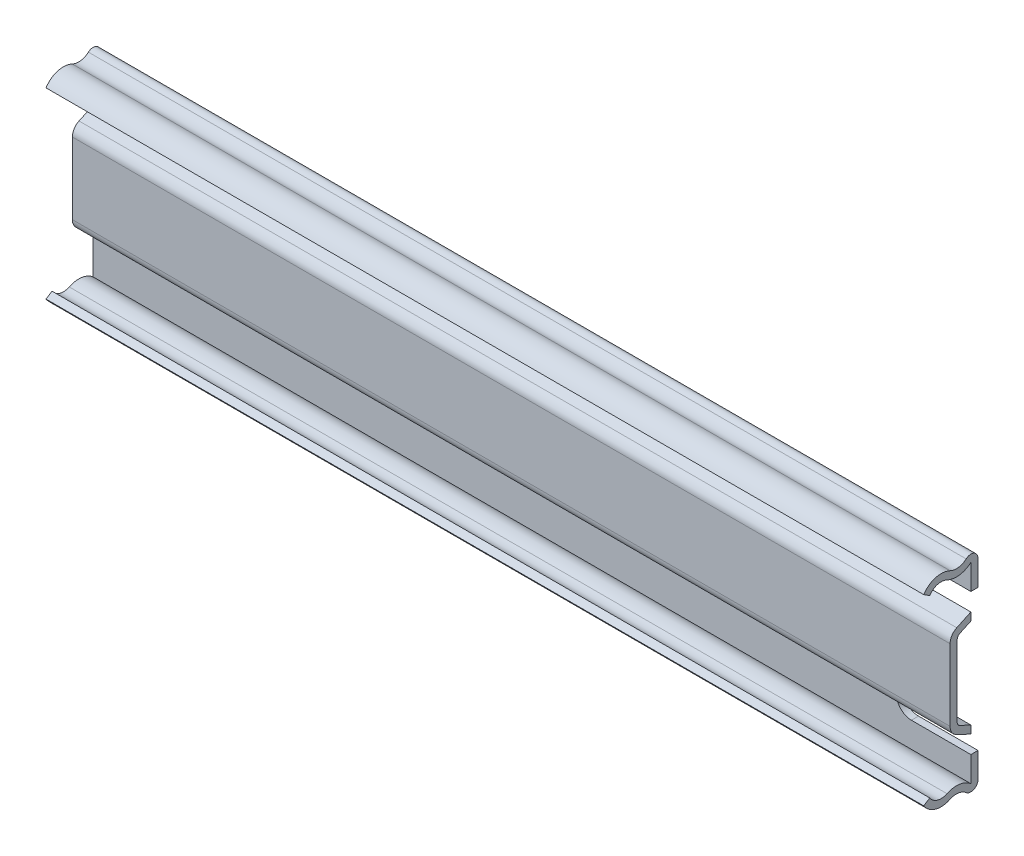
SolidWorks part; units mm, degrees
material "AISI 316 Annealed Stainless Steel Bar (SS)"
ref_plane "Front Plane" through (0, 0, 0) normal (0, 0, 1) x (1, 0, 0)
ref_plane "Top Plane" through (0, 0, 0) normal (0, 1, 0) x (1, 0, 0)
ref_plane "Right Plane" through (0, 0, 0) normal (1, 0, 0) x (0, 0, -1)
ref_plane "Plane1" through (-3.937, 0, 0) normal (1, 0, 0) x (0, 0, -1)
sketch "Sketch1" plane through (-3.937, 0, 0) normal (1, 0, 0) x (0, 0, -1)
  line L0 (2.3114, 16.3766) -> (2.3114, -16.3766)
  line L1 (-4.7105, -14.9753) -> (-5.7404, -15.6277)
  line L2 (3.5306, -16.3766) -> (3.5306, 16.3766)
  line L3 (-5.7404, 15.6277) -> (-4.7105, 14.9753)
  arc A0 (2.3114, -16.3766) -> (-1.7707, -15.816) centre (-0.1524, -19.1744) ccw
  arc A1 (-1.7707, -15.816) -> (-4.7105, -14.9753) centre (-2.7686, -13.7451) cw
  arc A2 (-5.7404, -15.6277) -> (-1.2415, -16.9143) centre (-2.7686, -13.7451) ccw
  arc A3 (-1.2415, -16.9143) -> (1.5056, -17.2916) centre (-0.1524, -19.1744) cw
  arc A4 (1.5056, -17.2916) -> (3.5306, -16.3766) centre (2.3114, -16.3766) ccw
  arc A5 (3.5306, 16.3766) -> (1.5056, 17.2916) centre (2.3114, 16.3766) ccw
  arc A6 (1.5056, 17.2916) -> (-1.2415, 16.9143) centre (-0.1524, 19.1744) cw
  arc A7 (-1.2415, 16.9143) -> (-5.7404, 15.6277) centre (-2.7686, 13.7451) ccw
  arc A8 (-4.7105, 14.9753) -> (-1.7707, 15.816) centre (-2.7686, 13.7451) cw
  arc A9 (-1.7707, 15.816) -> (2.3114, 16.3766) centre (-0.1524, 19.1744) ccw
  dimension "D1" = 3.728
  dimension "D2" = 2.2987
  dimension "D3" = 3.5179
  dimension "D4" = 1.2192
  dimension "D5" = 2.025
  dimension "D6" = 4.7721
  dimension "D7" = 8.2411
  dimension "D8" = 9.271
  dimension "D9" = 32.9195
  dimension "D10" = 34.1496
extrude "Boss-Extrude1" add sketch "Sketch1" against normal blind 150
sketch "Sketch2" plane through (0, 0, -3.5306) normal (0, 0, -1) x (-1, 0, 0)
  line L0 (3.937, 12.065) -> (3.937, -12.065)
  line L1 (3.937, -12.065) -> (16.637, -12.065)
  line L2 (16.637, -12.065) -> (16.637, 12.065)
  line L3 (16.637, 12.065) -> (3.937, 12.065)
  line L4 (3.937, -16.3766) -> (3.937, 16.3766) construction
  line L5 (153.937, -16.3766) -> (3.937, -16.3766) construction
  dimension "D1" = 12.7
  dimension "D2" = 4.3116
  dimension "D3" = 28.4416
extrude "Cut-Extrude1" cut sketch "Sketch2" against normal through all
sketch "Sketch3" plane through (0, 0, -2.3114) normal (0, 0, 1) x (1, 0, 0)
  line L0 (-153.931, -7.3781) -> (-153.931, 7.3781)
  line L1 (-153.931, 7.3781) -> (-3.937, 7.3781)
  line L2 (-3.937, 7.3781) -> (-3.937, -7.3781)
  line L3 (-3.937, -7.3781) -> (-153.931, -7.3781)
  line L4 (-153.937, 16.3766) -> (-153.937, -16.3766) construction
  line L5 (-153.937, 16.3766) -> (-3.937, 16.3766) construction
  dimension "D1" = 150
  dimension "D2" = 8.9985
  dimension "D3" = 23.7547
extrude "Boss-Extrude2" add sketch "Sketch3" along normal blind 3.556
sketch "Sketch4" plane through (-153.937, 0, 0) normal (-1, 0, 0) x (0, 0, 1)
  line L0 (-3.5306, 6.6014) -> (-3.5306, -6.6014)
  line L1 (-3.5306, -6.6014) -> (0.0254, -6.6014)
  line L2 (0.0254, -6.6014) -> (0.0254, 6.6014)
  line L3 (0.0254, 6.6014) -> (-3.5306, 6.6014)
  line L4 (-3.5306, -16.3766) -> (-3.5306, 16.3766) construction
  dimension "D1" = 3.556
  dimension "D2" = 10.6902
  dimension "D3" = 23.8929
extrude "Cut-Extrude2" cut sketch "Sketch4" against normal through all
draft "Draft1" type of draft neutral plane draft angle 25 faces to draft 2 face at (-66.4746, 7.3781, -0.889) face at (-66.4746, -7.3781, -0.889) neutral plane through (0, 0, 1.2446) neutral plane normal (0, 0, 1) parameters "D1"=25
draft "Draft2" type of draft neutral plane draft angle 25 faces to draft 2 face at (-82.1105, 6.6014, -2.032) face at (-82.1105, -6.6014, -2.032) neutral plane through (-3.937, -6.6014, 0.0254) neutral plane normal (0, 0, -1) parameters "D1"=25
fillet "Fillet1" radius 0.762 4 edges at (-78.934, 6.6014, 0.0254) (-78.934, -6.6014, 0.0254) (-85.284, 9.0363, -2.3114) (-85.284, -9.0363, -2.3114) tangent propagation no
fillet "Fillet2" radius 1.9812 4 edges at (-85.287, 8.2596, -3.5306) (-78.934, 7.3781, 1.2446) (-78.934, -7.3781, 1.2446) (-85.287, -8.2596, -3.5306) tangent propagation no
fillet "Fillet3" radius 2.54 2 edges at (-16.637, -12.065, -2.921) (-16.637, 12.065, -2.921) tangent propagation no
